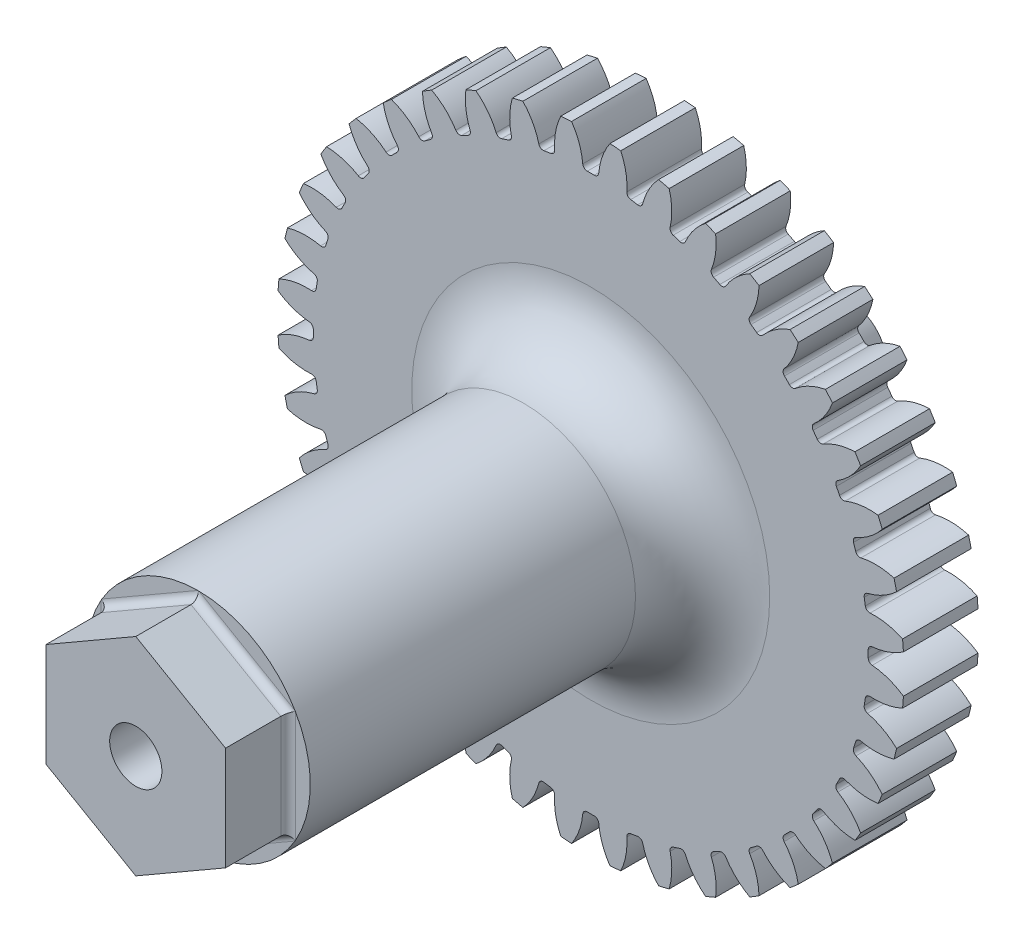
SolidWorks part; units mm, degrees
other "Markup1"
sketch "Sketch8" plane through (20.9607, 20.9607, 33) normal (0.6362, 0.3107, 0.7062) x (0.7675, -0.1618, -0.6203)
ref_plane "Front Plane" through (0, 0, 0) normal (0, 0, 1) x (1, 0, 0)
ref_plane "Top Plane" through (0, 0, 0) normal (0, 1, 0) x (1, 0, 0)
ref_plane "Right Plane" through (0, 0, 0) normal (1, 0, 0) x (0, 0, -1)
sketch "Sketch1" plane through (0, 0, 0) normal (0, 0, 1) x (1, 0, 0)
  circle A2 centre (0, 0) radius 20
  circle A3 centre (0, 0) radius 21
  circle A4 centre (0, 0) radius 18.6
  dimension "D1" = 40
  dimension "D2" = 42
  dimension "D3" = 2.4
extrude "Boss-Extrude1" add sketch "Sketch1" along normal mid plane 5 contours A3
sketch "Sketch3" plane through (0, 0, 2.5) normal (0, 0, 1) x (1, 0, 0)
  line L0 (0, 0) -> (0, 21) construction
  line L1 (-0.7852, 19.9846) -> (0.7852, 19.9846) construction
  line L2 (0, 0) -> (-0.5197, 18.5927) construction
  line L3 (0, 17.8273) -> (-1.5001, 21.9488) construction
  line L4 (0, 0) -> (1.6476, 20.9353) construction
  line L5 (0.7852, 19.9846) -> (2.3507, 19.8614) construction
  circle A0 centre (0, 0) radius 21 construction
  arc A1 (-2.1396, 21.8957) -> (-0.5197, 18.5927) centre (-4.9494, 18.4689) cw
  arc A2 (2.1396, 21.8957) -> (0.5197, 18.5927) centre (4.9494, 18.4689) ccw
  circle A3 centre (0, 0) radius 18.6 construction
  arc A4 (0.5197, 18.5927) -> (-0.5197, 18.5927) centre (0, 0) ccw
  circle A5 centre (0, 0) radius 20 construction
  circle A6 centre (0, 0) radius 21 construction
  circle A7 centre (0, 0) radius 22
  arc A8 (2.1396, 21.8957) -> (-2.1396, 21.8957) centre (0, 0) ccw
  dimension "D2" = 20
  dimension "D3" = 4.5
extrude "Cut-Extrude1" cut sketch "Sketch3" against normal through all both and the other way through all
fillet "Fillet1" radius 0.3 2 edges at (0.5197, 18.5927, 0) (-0.5197, 18.5927, 0)
pattern_circular "CirPattern1" count 40 over 360 about axis through (0, 0, 2.5) along (0, 0, -1) of "Cut-Extrude1", "Fillet1"
sketch "Sketch4" plane through (0, 0, 2.5) normal (0, 0, 1) x (1, 0, 0)
  circle A0 centre (0, 0) radius 7.5
  dimension "D1" = 15
extrude "Wheelshaft" add sketch "Sketch4" along normal blind 26.3
sketch "Sketch5" plane through (0, 0, -2.5) normal (0, 0, -1) x (-1, 0, 0)
  circle A0 centre (0, 0) radius 2.8
  dimension "D1" = 5.6
extrude "Boss-Extrude3" add sketch "Sketch5" along normal blind 12.43
fillet "Fillet3" radius 7.4 1 edges at (2.8, 0, -2.5)
chamfer "Chamfer1" distance 1.5 angle 15 1 edges at (-2.8, 0, -14.93) first distance on face at (2.8, 0, -9.9)
fillet "Fillet4" radius 4.5 1 edges at (7.5, 0, 2.5)
sketch "Sketch6" plane through (0, 0, 28.8) normal (0, 0, 1) x (1, 0, 0)
  line L1 (0, 6.95) -> (-6.0189, 3.475)
  line L2 (-6.0189, 3.475) -> (-6.0189, -3.475)
  line L3 (-6.0189, -3.475) -> (0, -6.95)
  line L4 (0, -6.95) -> (6.0189, -3.475)
  line L5 (6.0189, -3.475) -> (6.0189, 3.475)
  line L6 (6.0189, 3.475) -> (0, 6.95)
  circle A0 centre (0, 0) radius 6.95 construction
  dimension "D1" = 13.9
extrude "Boss-Extrude4" add sketch "Sketch6" along normal blind 4.2
sketch "Sketch7" plane through (0, 0, 33) normal (0, 0, 1) x (1, 0, 0)
  circle A0 centre (0, 0) radius 1.75
  dimension "D1" = 3.5
extrude "Cut-Extrude2" cut sketch "Sketch7" against normal blind 7
fillet "Fillet5" radius 0.5 6 edges at (3.0094, 5.2125, 28.8) (-6.0189, 0, 28.8) (-3.0094, -5.2125, 28.8) (3.0094, -5.2125, 28.8) (6.0189, 0, 28.8) (-3.0094, 5.2125, 28.8)
equation "\"Module\"= 1mm"
equation "\"Number of Teeth\"= 40"
equation "\"D1@Sketch1\"=\"Module\" * \"Number of Teeth\""
equation "\"D2@Sketch1\"=(\"Number of Teeth\" + 2) * \"Module\""
equation "\"D3@Sketch1\"=\"Module\" * if( \"Module\"=>1.25,2.25,2.4)"
equation "\"D3@Sketch3\"=180 / \"Number of Teeth\""
equation "\"D1@Fillet1\"=0.3 * \"Module\""
equation "\"D1@CirPattern1\"=\"Number of Teeth\""
